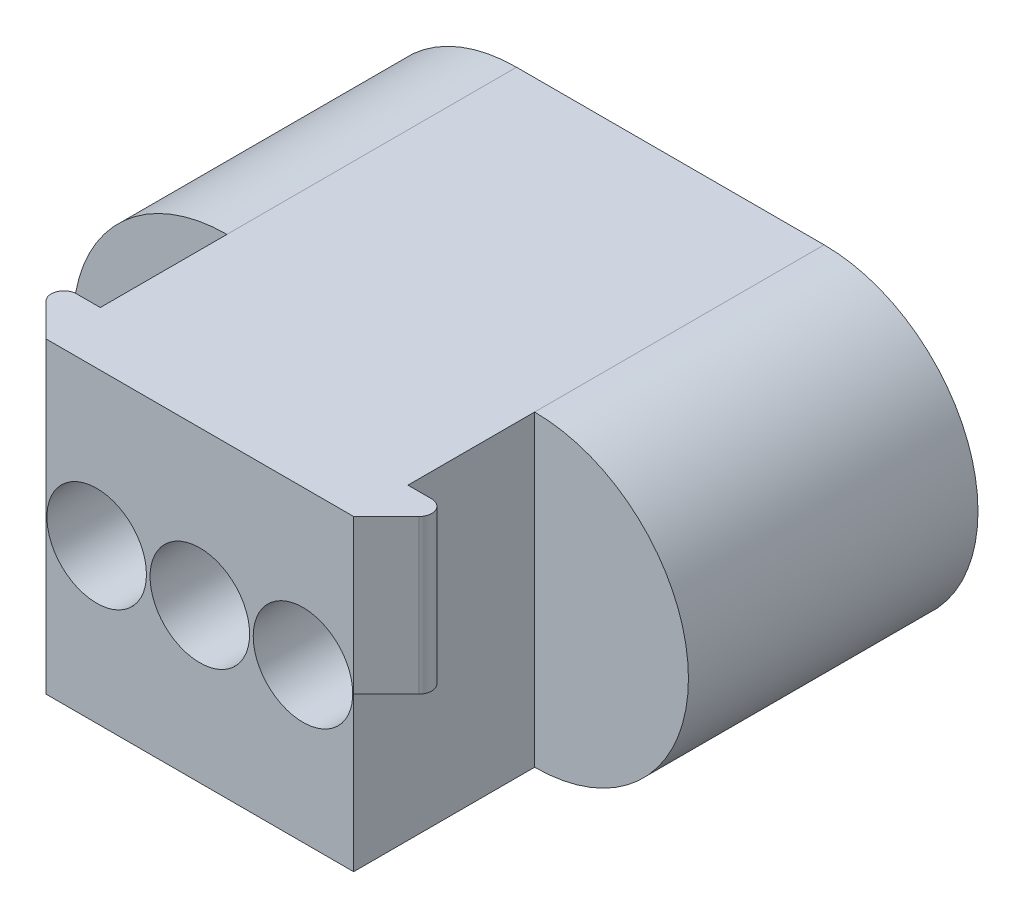
SolidWorks part; units mm, degrees
ref_plane "正面" through (0, 0, 0) normal (0, 0, 1) x (1, 0, 0)
ref_plane "平面" through (0, 0, 0) normal (0, 1, 0) x (1, 0, 0)
ref_plane "右側面" through (0, 0, 0) normal (1, 0, 0) x (0, 0, -1)
sketch "ｽｹｯﾁ1" plane through (0, 0, 0) normal (0, 0, 1) x (1, 0, 0)
  line L0 (8.5, 0) -> (-8.5, 0) construction
  line L1 (8.5, -8.5) -> (-8.5, -8.5)
  line L2 (8.5, 8.5) -> (-8.5, 8.5)
  arc A0 (8.5, -8.5) -> (8.5, 8.5) centre (8.5, 0) ccw
  arc A1 (-8.5, 8.5) -> (-8.5, -8.5) centre (-8.5, 0) ccw
  point P2 (0, 0)
  dimension "D1" = 8.5
  dimension "D2" = 17
extrude "ﾎﾞｽ - 押し出し1" add sketch "ｽｹｯﾁ1" along normal blind 26
sketch "ｽｹｯﾁ2" plane through (0, 0, 26) normal (0, 0, 1) x (1, 0, 0)
  line L0 (-8.5, 8.5) -> (-8.5, -8.5)
  line L1 (0, 8.5) -> (0, -8.5) construction
  line L2 (8.5, 8.5) -> (-8.5, 8.5) construction
  line L3 (-8.5, -8.5) -> (8.5, -8.5) construction
  line L4 (8.5, 8.5) -> (8.5, -8.5)
  arc A0 (-8.5, 8.5) -> (-8.5, -8.5) centre (-8.5, 0) ccw construction
  arc A1 (-8.5, 8.5) -> (-8.5, -8.5) centre (-8.5, 0) ccw
  arc A2 (8.5, 8.5) -> (8.5, -8.5) centre (8.5, 0) cw
extrude "ｶｯﾄ - 押し出し1" cut sketch "ｽｹｯﾁ2" against normal blind 10
sketch "ｽｹｯﾁ3" plane through (8.5, 0, 0) normal (1, 0, 0) x (0, 0, -1)
  line L0 (-26, 8.5) -> (-26, -8.5) construction
  line L1 (-26, 0) -> (-23, 0)
  line L2 (-26, 0) -> (-26, 8.5)
  line L3 (-26, 8.5) -> (-23, 8.5)
  line L4 (-23, 0) -> (-23, 8.5)
  line L5 (-26, 8.5) -> (-16, 8.5) construction
  dimension "D1" = 3
extrude "ﾎﾞｽ - 押し出し2" add sketch "ｽｹｯﾁ3" along normal blind 3
sketch "ｽｹｯﾁ4" plane through (0, 8.5, 0) normal (0, 1, 0) x (1, 0, 0)
  line L0 (11.5, -23) -> (11.5, -26)
  line L1 (11.5, -26) -> (8.5, -26)
  line L3 (8.5, -26) -> (11.5, -23)
  line L4 (8.5, -23) -> (8.5, -26) construction
  line L5 (11.5, -26) -> (-8.5, -26) construction
extrude "ｶｯﾄ - 押し出し2" cut sketch "ｽｹｯﾁ4" against normal up to next
sketch "ｽｹｯﾁ5" plane through (-8.5, 0, 0) normal (-1, 0, 0) x (0, 0, 1)
  line L0 (26, -8.5) -> (26, 8.5) construction
  line L1 (26, 0) -> (23, 0)
  line L2 (26, 0) -> (26, 8.5)
  line L3 (26, 8.5) -> (23, 8.5)
  line L4 (23, 0) -> (23, 8.5)
  line L5 (26, 8.5) -> (16, 8.5) construction
  point P8 (23, 4.25)
  dimension "D1" = 3
extrude "ﾎﾞｽ - 押し出し3" add sketch "ｽｹｯﾁ5" along normal blind 3
sketch "ｽｹｯﾁ6" plane through (0, 8.5, 0) normal (0, 1, 0) x (1, 0, 0)
  line L0 (-8.5, -23) -> (-8.5, -26) construction
  line L1 (8.5, -26) -> (-11.5, -26) construction
  line L2 (-11.5, -26) -> (-11.5, -23)
  line L3 (-11.5, -23) -> (-8.5, -26)
  line L4 (-8.5, -26) -> (-11.5, -26)
extrude "ｶｯﾄ - 押し出し3" cut sketch "ｽｹｯﾁ6" against normal up to next
sketch "ｽｹｯﾁ7" plane through (0, -8.5, 0) normal (0, -1, 0) x (1, 0, 0)
  line L0 (-8.5, 0) -> (8.5, 0) construction
  line L1 (-5.5, 3) -> (5.5, 3)
  line L2 (-5.5, 3) -> (-5.5, 23)
  line L3 (-5.5, 23) -> (5.5, 23)
  line L4 (5.5, 3) -> (5.5, 23)
  line L5 (-8.5, 26) -> (8.5, 26) construction
  line L6 (-8.5, 16) -> (-8.5, 0) construction
  line L7 (8.5, 26) -> (8.5, 16) construction
  dimension "D1" = 3
  dimension "D2" = 3
  dimension "D3" = 3
  dimension "D4" = 3
extrude "ｶｯﾄ - 押し出し4" cut sketch "ｽｹｯﾁ7" against normal blind 2
fillet "ﾌｨﾚｯﾄ3" radius 1 1 edges at (5.5, -7.5, 3) type face fillet first side face at (0, -7.5, 3) second side face at (5.5, -7.5, 13)
fillet "ﾌｨﾚｯﾄ4" radius 1 1 edges at (-5.5, -7.5, 3) type face fillet first side face at (-0.5, -7.5, 3) second side face at (-5.5, -7.5, 13)
sketch "ｽｹｯﾁ10" plane through (0, -8.5, 0) normal (0, -1, 0) x (1, 0, 0)
  line L0 (-8.5, 26) -> (-8.5, 16) construction
  line L1 (-7.5, 23) -> (7.5, 23)
  line L2 (-7.5, 23) -> (-7.5, 16)
  line L3 (-7.5, 16) -> (7.5, 16)
  line L4 (7.5, 23) -> (7.5, 16)
  line L5 (8.5, 26) -> (8.5, 16) construction
  line L6 (-8.5, 26) -> (8.5, 26) construction
  line L7 (-8.5, 0) -> (8.5, 0) construction
  dimension "D1" = 1
  dimension "D2" = 1
  dimension "D3" = 3
  dimension "D4" = 16
extrude "ｶｯﾄ - 押し出し5" cut sketch "ｽｹｯﾁ10" against normal blind 2
sketch "ｽｹｯﾁ11" plane through (0, -8.5, 0) normal (0, -1, 0) x (1, 0, 0)
  line L0 (0, 26) -> (0, 0) construction
  line L1 (-8.5, 26) -> (8.5, 26) construction
  line L2 (-8.5, 0) -> (8.5, 0) construction
  line L3 (6.5, 21) -> (3.5, 21)
  line L4 (3.5, 21) -> (3.5, 5)
  line L5 (3.5, 5) -> (0, 5)
  line L6 (0, 5) -> (0, 3.0016)
  line L7 (0, 3.0016) -> (4.5, 3)
  line L8 (6.5, 21) -> (6.5, 16)
  line L10 (6.5, 16) -> (5.5, 16)
  line L11 (5.5, 16) -> (5.5, 4)
  line L12 (8.5, 26) -> (8.5, 16) construction
  arc A0 (4.5, 3) -> (5.5, 4) centre (4.5, 4) ccw construction
  arc A1 (4.5, 3) -> (5.5, 4) centre (4.5, 4) ccw
  dimension "D1" = 4.5
  dimension "D2" = 5
  dimension "D3" = 5
  dimension "D4" = 2
  dimension "D5" = 5
extrude "ｶｯﾄ - 押し出し6" cut sketch "ｽｹｯﾁ11" against normal blind 4
mirror "ﾐﾗｰ1" about plane through (0, 0, 0) normal (1, 0, 0) of "ｶｯﾄ - 押し出し6"
fillet "ﾌｨﾚｯﾄ5" radius 0.5 1 edges at (3.5, -5.5, 5)
fillet "ﾌｨﾚｯﾄ6" radius 0.5 1 edges at (-3.5, -5.5, 5)
fillet "ﾌｨﾚｯﾄ7" radius 1 4 edges at (6.5, -5.5, 21) (3.5, -5.5, 21) (-6.5, -5.5, 21) (-3.5, -5.5, 21)
fillet "ﾌｨﾚｯﾄ9" radius 0.7 1 edges at (-11.5, 4.25, 23)
fillet "ﾌｨﾚｯﾄ10" radius 0.7 1 edges at (11.5, 4.25, 23)
sketch "ｽｹｯﾁ12" plane through (0, -8.5, 0) normal (0, -1, 0) x (1, 0, 0)
  line L0 (-8.5, 16) -> (-8.5, 0) construction
  line L1 (-1.5, 11) -> (1.5, 11)
  line L2 (-1.5, 11) -> (-1.5, 7)
  line L3 (-1.5, 7) -> (1.5, 7)
  line L4 (1.5, 11) -> (1.5, 7)
  line L5 (8.5, 16) -> (8.5, 0) construction
  line L6 (-8.5, 0) -> (8.5, 0) construction
  dimension "D1" = 7
  dimension "D2" = 7
  dimension "D3" = 7
  dimension "D4" = 11
extrude "ｶｯﾄ - 押し出し7" cut sketch "ｽｹｯﾁ12" against normal blind 4
fillet "ﾌｨﾚｯﾄ11" radius 1.5 1 edges at (0, -6.5, 23)
fillet "ﾌｨﾚｯﾄ12" radius 0.5 1 edges at (0, -8.5, 23)
sketch "ｽｹｯﾁ13" plane through (0, 0, 26) normal (0, 0, 1) x (1, 0, 0)
  line L0 (0, 8.5) -> (0, -8.5) construction
  line L1 (8.5, 8.5) -> (-8.5, 8.5) construction
  line L2 (-8.5, -8.5) -> (8.5, -8.5) construction
  line L3 (-8.5, 0) -> (8.5, 0) construction
  line L5 (-8.5, -8.5) -> (-8.5, 0) construction
  circle A2 centre (0, 0) radius 2.75
  circle A3 centre (-5.7, 0) radius 2.75
  circle A4 centre (5.7, 0) radius 2.75
  dimension "D1" = 2.8
  dimension "D2" = 5.5
extrude "ｶｯﾄ - 押し出し16" cut sketch "ｽｹｯﾁ13" against normal blind 10
sketch "ｽｹｯﾁ14" plane through (0, 0, 0) normal (0, 0, -1) x (-1, 0, 0)
  line L0 (8.5, -8.5) -> (-8.5, -8.5) construction
  line L1 (8.5, 1.5) -> (-8.5, 1.5)
  line L2 (8.5, 1.5) -> (8.5, -1.5)
  line L3 (8.5, -1.5) -> (-8.5, -1.5)
  line L4 (-8.5, 1.5) -> (-8.5, -1.5)
  line L5 (8.5, 1.5) -> (-8.5, -1.5) construction
  line L6 (8.5, -1.5) -> (-8.5, 1.5) construction
  line L7 (8.5, 0) -> (-8.5, 0) construction
  line L8 (8.5, -6) -> (-8.5, -6)
  line L9 (8.5, 6) -> (-8.5, 6)
  line L10 (-8.5, 8.5) -> (8.5, 8.5) construction
  arc A0 (8.5, -6) -> (8.5, 6) centre (8.5, 0) ccw
  arc A1 (-8.5, 6) -> (-8.5, -6) centre (-8.5, 0) ccw
  point P0 (0, 0)
  point P10 (0, 0)
  dimension "D1" = 7
  dimension "D2" = 17
  dimension "D3" = 2.5
extrude "ｶｯﾄ - 押し出し20" cut sketch "ｽｹｯﾁ14" against normal blind 15
fillet "ﾌｨﾚｯﾄ13" radius 0.7 4 edges at (8.5, -1.5, 7.5) (8.5, 1.5, 7.5) (-8.5, 1.5, 7.5) (-8.5, -1.5, 7.5)
sketch "ｽｹｯﾁ15" plane through (0, 0, 0) normal (0, 0, -1) x (-1, 0, 0)
  line L0 (0, 1.5) -> (0, -1.5) construction
  line L1 (7.8, 1.5) -> (-7.8, 1.5) construction
  line L2 (-7.8, -1.5) -> (7.8, -1.5) construction
  line L3 (-8.5, 0.8) -> (-8.5, -0.8) construction
  line L4 (-6, 1) -> (-7.5, 1)
  line L5 (-6, 1) -> (-6, -1)
  line L6 (-6, -1) -> (-7.5, -1)
  line L7 (-7.5, 1) -> (-7.5, -1)
  line L8 (6, 1) -> (7.5, 1)
  line L9 (0.75, 1) -> (-0.75, 1)
  line L10 (0.75, 1) -> (0.75, -1)
  line L11 (0.75, -1) -> (-0.75, -1)
  line L12 (-0.75, 1) -> (-0.75, -1)
  line L13 (0.75, 1) -> (-0.75, -1) construction
  line L14 (0.75, -1) -> (-0.75, 1) construction
  line L15 (6, 1) -> (6, -1)
  line L16 (6, -1) -> (7.5, -1)
  line L17 (7.5, 1) -> (7.5, -1)
  point P12 (0, 0)
  dimension "D1" = 1
  dimension "D2" = 0.5
  dimension "D3" = 0.5
  dimension "D4" = 1.5
  dimension "D5" = 1.5
  dimension "D6" = 0.5
extrude "ｶｯﾄ - 押し出し22" cut sketch "ｽｹｯﾁ15" against normal blind 15
